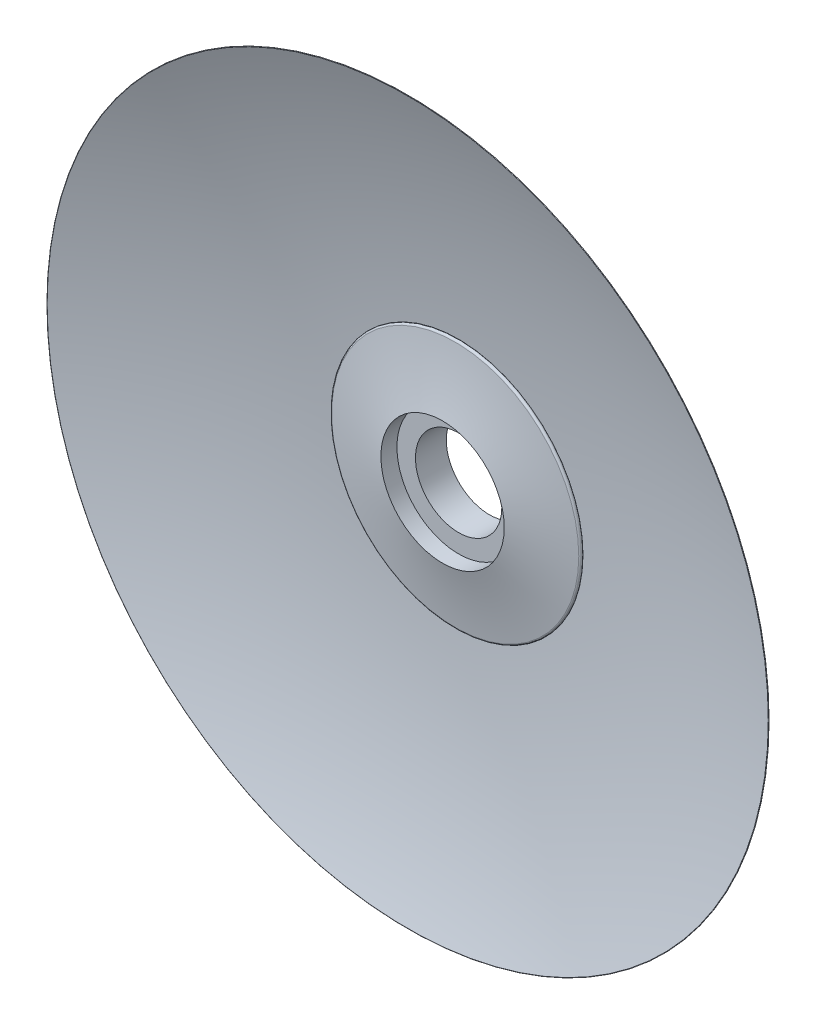
SolidWorks part; units mm, degrees
ref_plane "Front Plane" through (0, 0, 0) normal (0, 0, 1) x (1, 0, 0)
ref_plane "Top Plane" through (0, 0, 0) normal (0, 1, 0) x (1, 0, 0)
ref_plane "Right Plane" through (0, 0, 0) normal (1, 0, 0) x (0, 0, -1)
sketch "Sketch2" plane through (0, 0, 0) normal (1, 0, 0) x (0, 0, -1)
  line L0 (0, 0) -> (148, 0)
  line L1 (0, 0) -> (0, 50)
  line L2 (0, 50) -> (133, 50)
  line L3 (125, 50) -> (125, 292.3639) construction
  line L4 (133, 50) -> (133, 292.3639) construction
  line L5 (116.9124, 80) -> (96.9124, 80)
  line L6 (86.9124, 70) -> (86.9124, 50)
  line L7 (133, 50) -> (148, 50)
  line L8 (148, 0) -> (148, 50)
  line L9 (0, 35) -> (148, 35)
  line L10 (0, 50) -> (-202, 50)
  line L11 (-202, 50) -> (-202, 0)
  line L12 (-202, 0) -> (0, 0)
  line L13 (0, 35) -> (-202, 35)
  arc A0 (125, 50) -> (81.7356, 292.2774) centre (-575, 50) ccw
  arc A1 (82.1991, 292.4643) -> (133, 50) centre (-471.0217, 50) cw
  arc A2 (81.7356, 292.2774) -> (82.1991, 292.4643) centre (81.9702, 292.3639) cw
  arc A3 (125, 50) -> (123.2043, 100.1074) centre (-575, 50) ccw
  arc A4 (120.2222, 100.2045) -> (110, 50) centre (-276.0421, 154.7451) cw
  arc A5 (120.2222, 100.2045) -> (123.2043, 100.1074) centre (121.7082, 100) cw
  arc A6 (127.7052, 129.8018) -> (133, 50) centre (-471.0217, 50) cw
  arc A7 (130.6282, 130.4328) -> (148, 50) centre (-362.4698, -18.1582) cw
  arc A8 (130.6282, 130.4328) -> (127.7052, 129.8018) centre (129.192, 130) ccw
  arc A9 (96.9124, 80) -> (86.9124, 70) centre (96.9124, 70) ccw
  point P13 (78.8348, 300)
  point P34 (86.9124, 80)
  dimension "D3" = 700
  dimension "D6" = 0.25
  dimension "D8" = 1.5
  dimension "D9" = 400
  dimension "D14" = 1.5
  dimension "D16" = 515
  dimension "D18" = 10
  dimension "D1" = 250
  dimension "D2" = 50
  dimension "D4" = 575
  dimension "D5" = 8
  dimension "D7" = 15
  dimension "D10" = 50
  dimension "D11" = 30
  dimension "D12" = 80
  dimension "D13" = 15
  dimension "D15" = 80
  dimension "D17" = 35
  dimension "D19" = 350
revolve "Revolve1" add sketch "Sketch2" angle 360 about L0 region at (0, 42.5, 101) region at (0, 42.5, -74) region at (0, 81.6658, -137.0337) region at (0, 69.5517, -119.564)
revolve "Revolve4" add sketch "Sketch2<4>" angle 360 about L0 region at (0, 145.0315, -118.9807)
sketch "Sketch2<4>" plane through (0, 0, 0) normal (1, 0, 0) x (0, 0, -1) same geometry as "Sketch2"
scale "Scale2" scale about centroid uniform scaling yes scale factor 0.2
sketch "Sketch3" plane through (0, 0, -4.273) normal (0, 0, 1) x (1, 0, 0)
  circle A0 centre (0, 0) radius 10
  dimension "D1" = 20
extrude "Cut-Extrude1" cut sketch "Sketch3" against normal blind 65
